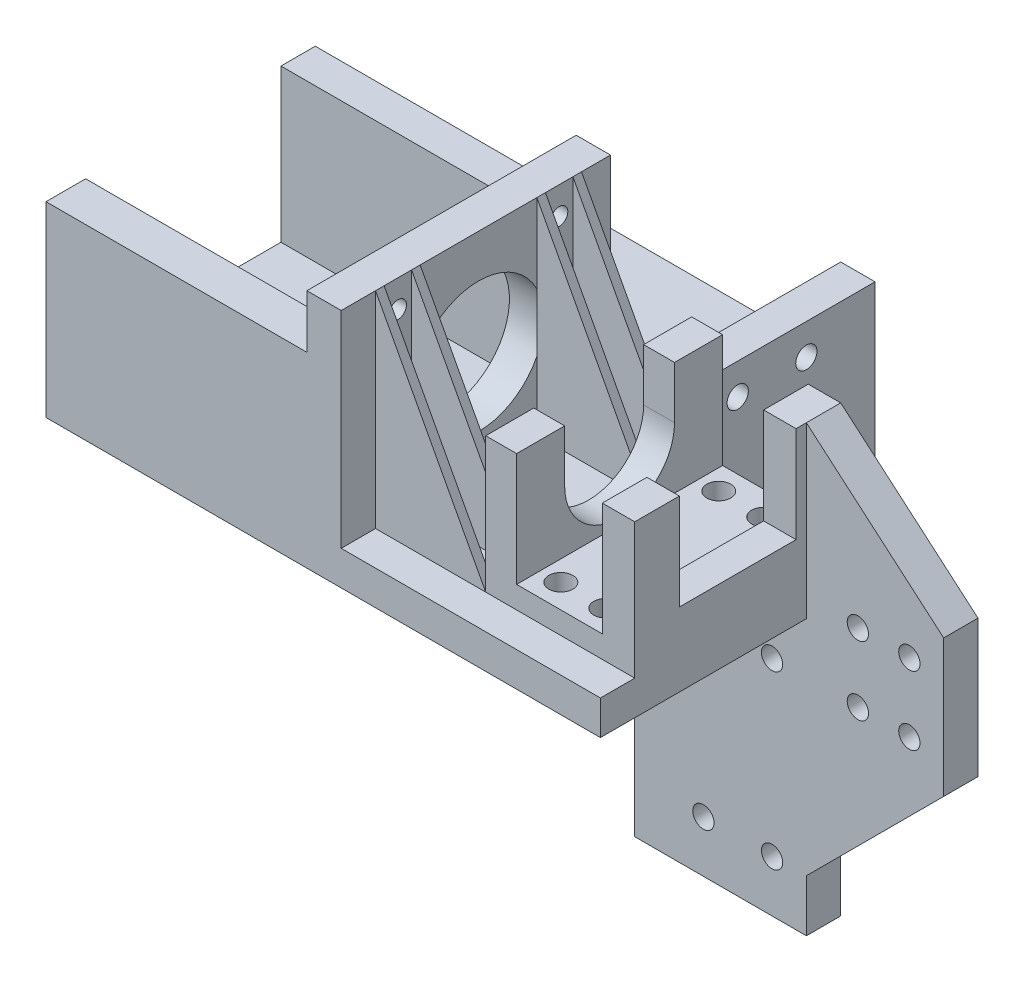
SolidWorks part; units mm, degrees
ref_plane "Front Plane" through (0, 0, 0) normal (0, 0, 1) x (1, 0, 0)
ref_plane "Top Plane" through (0, 0, 0) normal (0, 1, 0) x (1, 0, 0)
ref_plane "Right Plane" through (0, 0, 0) normal (1, 0, 0) x (0, 0, -1)
sketch "Sketch1" plane through (0, 0, 0) normal (0, 1, 0) x (1, 0, 0)
  line L0 (0, 0) -> (161.51, 0)
  line L1 (161.51, 0) -> (161.51, 70)
  line L2 (161.51, 70) -> (121.51, 70)
  line L3 (121.51, 70) -> (121.51, 120)
  line L4 (121.51, 120) -> (0, 120)
  line L5 (0, 120) -> (0, 0)
  dimension "D1" = 40
  dimension "D2" = 161.51
  dimension "D3" = 70
  dimension "D4" = 120
extrude "Boss-Extrude1" add sketch "Sketch1" along normal blind 10
sketch "Sketch2" plane through (0, 10, 0) normal (0, 1, 0) x (1, 0, 0)
  line L1 (161.51, 70) -> (152.06, 70)
  line L2 (161.51, 70) -> (161.51, 10)
  line L3 (161.51, 10) -> (152.06, 10)
  line L4 (152.06, 70) -> (152.06, 10)
  line L5 (0, 0) -> (161.51, 0) construction
  dimension "D1" = 9.45
  dimension "D2" = 10
extrude "Boss-Extrude2" add sketch "Sketch2" along normal blind 39.45
sketch "Sketch3" plane through (0, 10, 0) normal (0, 1, 0) x (1, 0, 0)
  line L1 (152.06, 70) -> (127.1, 70)
  line L2 (152.06, 70) -> (152.06, 10)
  line L3 (152.06, 10) -> (127.1, 10)
  line L4 (127.1, 70) -> (127.1, 10)
  line L5 (0, 0) -> (161.51, 0) construction
  dimension "D1" = 24.96
  dimension "D2" = 10
extrude "Boss-Extrude3" add sketch "Sketch3" along normal blind 6.45
sketch "Sketch4" plane through (0, 10, 0) normal (0, 1, 0) x (1, 0, 0)
  line L1 (127.1, 70) -> (118.1, 70)
  line L2 (127.1, 70) -> (127.1, 10)
  line L3 (127.1, 10) -> (118.1, 10)
  line L4 (118.1, 70) -> (118.1, 10)
  line L5 (0, 0) -> (161.51, 0) construction
  dimension "D1" = 9
  dimension "D2" = 10
extrude "Boss-Extrude4" add sketch "Sketch4" along normal blind 39.45
sketch "Sketch5" plane through (161.51, 0, 0) normal (1, 0, 0) x (0, 0, -1)
  line L0 (10, 49.45) -> (70, 49.45) construction
  line L1 (23, 49.45) -> (57, 49.45)
  line L2 (23, 49.45) -> (23, 21.45)
  line L3 (23, 21.45) -> (57, 21.45)
  line L4 (57, 49.45) -> (57, 21.45)
  line L5 (10, 49.45) -> (10, 10) construction
  dimension "D1" = 34
  dimension "D2" = 28
  dimension "D3" = 13
extrude "Cut-Extrude1" cut sketch "Sketch5" against normal up to next
sketch "Sketch6" plane through (127.1, 0, 0) normal (1, 0, 0) x (0, 0, -1)
  line L0 (24, 49.45) -> (24, 34.24)
  line L1 (10, 49.45) -> (70, 49.45) construction
  line L2 (56, 49.45) -> (56, 34.24)
  line L3 (40, 49.45) -> (40, 0) construction
  line L5 (24, 49.45) -> (56, 49.45)
  line L8 (10, 49.45) -> (70, 49.45) construction
  line L9 (0, 0) -> (70, 0) construction
  arc A0 (24, 34.24) -> (56, 34.24) centre (40, 34.24) ccw
  dimension "D2" = 16
  dimension "D1" = 15.21
extrude "Cut-Extrude2" cut sketch "Sketch6" against normal up to next
sketch "Sketch7" plane through (0, 10, 0) normal (0, 1, 0) x (1, 0, 0)
  line L1 (0, 11.55) -> (76, 11.55)
  line L2 (0, 11.55) -> (0, 0)
  line L3 (0, 0) -> (76, 0)
  line L4 (76, 11.55) -> (76, 0)
  line L5 (0, 120) -> (0, 0) construction
  dimension "D1" = 11.55
  dimension "D2" = 76
extrude "Boss-Extrude5" add sketch "Sketch7" along normal blind 44.46
sketch "Sketch8" plane through (0, 10, 0) normal (0, 1, 0) x (1, 0, 0)
  line L0 (0, 120) -> (0, 11.55) construction
  line L1 (0, 78.45) -> (76, 78.45)
  line L2 (0, 78.45) -> (0, 68.45)
  line L3 (0, 68.45) -> (76, 68.45)
  line L4 (76, 78.45) -> (76, 68.45)
  line L5 (76, 11.55) -> (0, 11.55) construction
  dimension "D1" = 76
  dimension "D2" = 10
  dimension "D3" = 56.9
extrude "Boss-Extrude6" add sketch "Sketch8" along normal blind 44.46
sketch "Sketch9" plane through (0, 10, 0) normal (0, 1, 0) x (1, 0, 0)
  line L1 (76, 78.45) -> (86, 78.45)
  line L2 (76, 78.45) -> (76, 0)
  line L3 (76, 0) -> (86, 0)
  line L4 (86, 78.45) -> (86, 0)
  dimension "D1" = 10
extrude "Boss-Extrude7" add sketch "Sketch9" along normal blind 60
sketch "Sketch10" plane through (86, 0, 0) normal (1, 0, 0) x (0, 0, -1)
  line L0 (0, 70) -> (78.45, 70) construction
  line L1 (70, 70) -> (67.5, 70)
  line L2 (70, 70) -> (70, 10)
  line L3 (70, 10) -> (67.5, 10)
  line L4 (67.5, 70) -> (67.5, 10)
  line L5 (70, 10) -> (120, 10) construction
  line L6 (0, 10) -> (78.45, 10) construction
  line L7 (59.5, 70) -> (57, 70)
  line L8 (59.5, 70) -> (59.5, 10)
  line L9 (59.5, 10) -> (57, 10)
  line L10 (57, 70) -> (57, 10)
  line L12 (23, 70) -> (20.5, 70)
  line L13 (23, 70) -> (23, 10)
  line L14 (23, 10) -> (20.5, 10)
  line L15 (20.5, 70) -> (20.5, 10)
  line L16 (10, 70) -> (12.5, 70)
  line L17 (10, 70) -> (10, 10)
  line L18 (10, 10) -> (12.5, 10)
  line L19 (12.5, 70) -> (12.5, 10)
  line L20 (0, 70) -> (0, 10) construction
  dimension "D1" = 10
  dimension "D2" = 2.5
  dimension "D3" = 8
  dimension "D4" = 2.5
  dimension "D5" = 34
  dimension "D6" = 2.5
  dimension "D7" = 8
  dimension "D8" = 2.5
extrude "Boss-Extrude8" add sketch "Sketch10" along normal up to surface (32.1 mm away) up to face at (118.1, 33.785, -40)
sketch "Sketch13" plane through (0, 0, -70) normal (0, 0, -1) x (-1, 0, 0)
  line L0 (-111.51, 0) -> (-161.51, 0)
  line L1 (-121.51, 0) -> (0, 0) construction
  line L2 (-161.51, 0) -> (-161.51, 49.45)
  line L3 (-161.51, 49.45) -> (-201.51, 15.1537)
  line L4 (-201.51, 15.1537) -> (-201.51, -24.8463)
  line L5 (-201.51, -24.8463) -> (-161.51, -64.85)
  line L6 (-161.51, -64.85) -> (-161.51, -80)
  line L7 (-161.51, -80) -> (-111.51, -80)
  line L8 (-111.51, -80) -> (-111.51, 0)
  dimension "D1" = 80
  dimension "D2" = 15.15
  dimension "D3" = 40
  dimension "D4" = 52.69
  dimension "D5" = 90
  dimension "D7" = 50
  dimension "D8" = 40
extrude "Boss-Extrude12" add sketch "Sketch13" against normal blind 10
sketch "Sketch16" plane through (0, 0, -70) normal (0, 0, -1) x (-1, 0, 0)
  line L0 (-86, 70) -> (-118.1, 70)
  line L1 (-118.1, 70) -> (-118.1, 10)
  line L2 (-121.51, 10) -> (-86, 10) construction
  line L3 (-118.1, 10) -> (-86, 70)
extrude "Cut-Extrude5" cut sketch "Sketch16" against normal through all
sketch "Sketch17" plane through (0, 0, 0) normal (0, -1, 0) x (1, 0, 0)
  line L1 (111.51, -70) -> (121.51, -70)
  line L2 (111.51, -70) -> (111.51, -120)
  line L3 (111.51, -120) -> (121.51, -120)
  line L4 (121.51, -70) -> (121.51, -120)
extrude "Boss-Extrude13" add sketch "Sketch17" along normal up to surface (80 mm away) up to face at (136.51, -80, -65)
sketch "Sketch18" plane through (0, 10, 0) normal (0, 1, 0) x (1, 0, 0)
  line L0 (118.1, 70) -> (86, 70) construction
  line L1 (121.51, 120) -> (111.51, 120)
  line L2 (121.51, 120) -> (121.51, 70)
  line L3 (121.51, 70) -> (111.51, 70)
  line L4 (111.51, 120) -> (111.51, 70)
  dimension "D1" = 10
extrude "Boss-Extrude14" add sketch "Sketch18" along normal blind 25
sketch "Sketch19" plane through (0, 16.45, 0) normal (0, 1, 0) x (1, 0, 0)
  line L0 (152.06, 70) -> (127.1, 70) construction
  line L1 (161.51, 10) -> (161.51, 23) construction
  circle A0 centre (146.1, 62.98) radius 3.5
  circle A1 centre (133, 62.98) radius 3.5
  circle A2 centre (133, 16.98) radius 3.5
  circle A3 centre (146.1, 16.98) radius 3.5
  dimension "D1" = 7
  dimension "D2" = 7.02
  dimension "D3" = 46
  dimension "D4" = 13.1
  dimension "D5" = 15.41
extrude "Cut-Extrude6" cut sketch "Sketch19" against normal blind 20
sketch "Sketch20" plane through (0, 0, -60) normal (0, 0, 1) x (1, 0, 0)
  line L0 (111.51, 0) -> (131.1644, 0) construction
  line L1 (126.1, 0) -> (153.1, 0)
  line L2 (126.1, 0) -> (126.1, -6)
  line L3 (126.1, -6) -> (153.1, -6)
  line L4 (153.1, 0) -> (153.1, -6)
  line L5 (111.51, -80) -> (111.51, 0) construction
  dimension "D1" = 14.59
  dimension "D2" = 27
  dimension "D3" = 6
extrude "Cut-Extrude7" cut sketch "Sketch20" against normal blind 10
sketch "Sketch21" plane through (76, 0, 0) normal (-1, 0, 0) x (0, 0, 1)
  line L0 (-78.45, 70) -> (0, 70) construction
  line L1 (-78.45, 70) -> (-78.45, 54.46) construction
  line L2 (-63.5, 61.95) -> (-16.5, 14.95) construction
  line L3 (-16.5, 61.95) -> (-63.5, 14.95) construction
  circle A0 centre (-16.5, 61.95) radius 2.51
  circle A1 centre (-63.5, 61.95) radius 2.51
  circle A2 centre (-63.5, 14.95) radius 2.51
  circle A3 centre (-16.5, 14.95) radius 2.51
  circle A4 centre (-40, 38.45) radius 19
  dimension "D1" = 5.02
  dimension "D6" = 38
  dimension "D2" = 8.05
  dimension "D3" = 14.95
  dimension "D4" = 47
  dimension "D5" = 47
extrude "Cut-Extrude8" cut sketch "Sketch21" against normal blind 10
sketch "Sketch22" plane through (0, 0, -70) normal (0, 0, -1) x (-1, 0, 0)
  line L0 (-161.51, -80) -> (-121.51, -80) construction
  line L1 (-121.51, 35) -> (-121.51, -80) construction
  line L2 (-201.51, 15.1537) -> (-151.51, 15.1537) construction
  line L3 (-201.51, 15.1537) -> (-201.51, -24.8463) construction
  circle A0 centre (-131.51, -15) radius 3.1
  circle A1 centre (-151.51, -15) radius 3.1
  circle A2 centre (-151.51, -65) radius 3.1
  circle A3 centre (-131.51, -65) radius 3.1
  circle A4 centre (-191.51, 5.1537) radius 3.1
  circle A5 centre (-176.51, 5.1537) radius 3.1
  circle A6 centre (-176.51, -14.8463) radius 3.1
  circle A7 centre (-191.51, -14.8463) radius 3.1
  dimension "D4" = 6.2
  dimension "D6" = 6.2
  dimension "D1" = 20
  dimension "D2" = 15
  dimension "D3" = 50
  dimension "D5" = 10
  dimension "D7" = 15
  dimension "D8" = 20
  dimension "D9" = 10
  dimension "D10" = 10
extrude "Cut-Extrude9" cut sketch "Sketch22" against normal blind 10
sketch "Sketch23" plane through (111.51, 0, 0) normal (-1, 0, 0) x (0, 0, 1)
  line L0 (-120, 35) -> (-70, 35) construction
  line L2 (-120, -80) -> (-120, 0) construction
  circle A0 centre (-100, 25.93) radius 3.1
  circle A1 centre (-80, 25.93) radius 3.1
  circle A2 centre (-80, -15.01) radius 3.1
  circle A3 centre (-100, -15.01) radius 3.1
  circle A4 centre (-100, -65.01) radius 3.1
  circle A5 centre (-80, -65.01) radius 3.1
  dimension "D1" = 6.2
  dimension "D2" = 50
  dimension "D3" = 40.94
  dimension "D4" = 9.07
  dimension "D5" = 20
  dimension "D6" = 20
extrude "Cut-Extrude10" cut sketch "Sketch23" against normal blind 10
